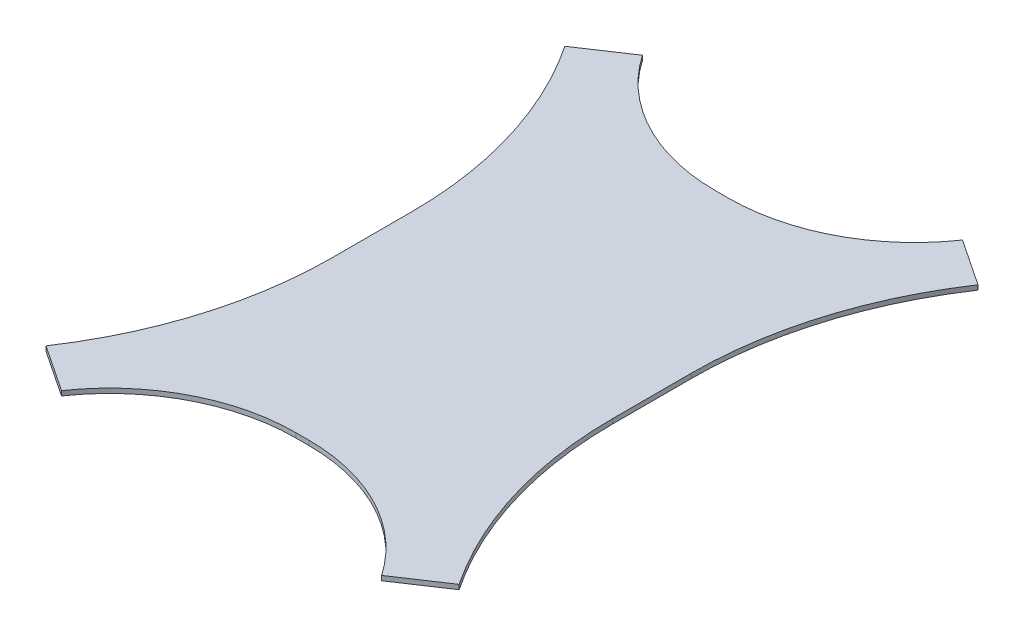
SolidWorks part; units mm, degrees
ref_plane "Ön Düzlem" through (0, 0, 0) normal (0, 0, 1) x (1, 0, 0)
ref_plane "Üst Düzlem" through (0, 0, 0) normal (0, 1, 0) x (1, 0, 0)
ref_plane "Sağ Düzlem" through (0, 0, 0) normal (1, 0, 0) x (0, 0, -1)
sketch "Çizim1" plane through (0, 0, 0) normal (0, 1, 0) x (1, 0, 0)
  line L1 (-60, 90) -> (60, 90)
  line L2 (-60, 90) -> (-60, -90)
  line L3 (-60, -90) -> (60, -90)
  line L4 (60, 90) -> (60, -90)
  line L5 (-60, 90) -> (60, -90) construction
  line L6 (-60, -90) -> (60, 90) construction
  point P0 (0, 0)
  point P6 (60, 90)
  dimension "D1" = 180
  dimension "D2" = 120
extrude "Yükseklik-Ekstrüzyon1" add sketch "Çizim1" along normal mid plane 2
sketch "Çizim2" plane through (0, 0, 0) normal (0, 1, 0) x (1, 0, 0)
  line L0 (-60, -90) -> (78.675, 118.0126)
  point P3 (90.2096, 135.3145)
  point P6 (88.7848, 133.1771)
  dimension "D1" = 250
ref_plane "Düzlem1" through (78.675, 0, -118.0126) normal (0.5547, 0, -0.8321) x (-0.8321, 0, -0.5547)
sketch "Çizim4" plane through (78.675, 0, -118.0126) normal (0.5547, 0, -0.8321) x (-0.8321, 0, -0.5547)
  line L0 (0, 1) -> (99.846, 1) construction
  line L1 (-12, 1) -> (12, 1)
  line L2 (-12, 1) -> (-12, -1)
  line L3 (-12, -1) -> (12, -1)
  line L4 (12, 1) -> (12, -1)
  point P4 (0, -1)
  point P8 (-12, 0)
  point P9 (0, 1)
  dimension "D1" = 24
  dimension "D2" = 2
extrude "Yükseklik-Ekstrüzyon3" add sketch "Çizim4" against normal up to next
mirror "Aynalama1" about plane through (0, 0, 0) normal (1, 0, 0) of "Yükseklik-Ekstrüzyon3"
mirror "Aynalama2" about plane through (0, 0, 0) normal (0, 0, 1) of "Aynalama1"
fillet "Radyus3" radius 80 2 edges at (45.5778, 0, -90) (-45.5778, 0, -90)
fillet "Radyus4" radius 80 2 edges at (-45.5778, 0, 90) (45.5778, 0, 90)
fillet "Radyus5" radius 170 2 edges at (-60, 0, 68.3667) (-60, 0, -68.3667)
fillet "Radyus6" radius 170 2 edges at (60, 0, -68.3667) (60, 0, 68.3667)
